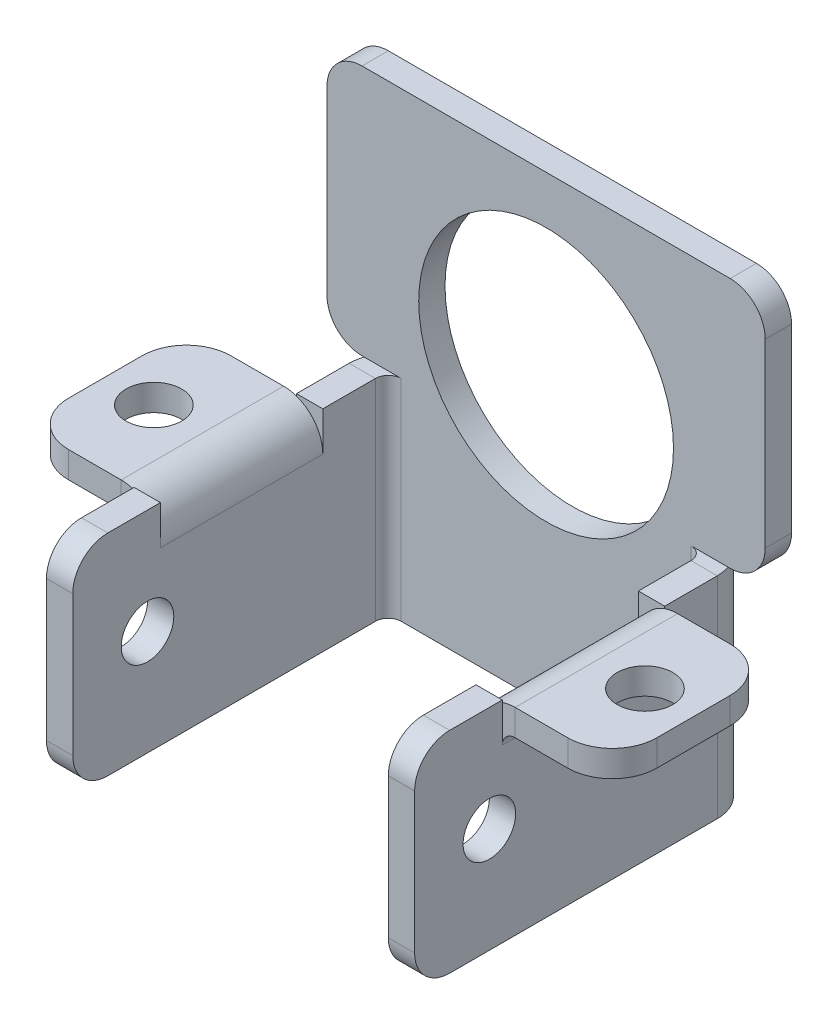
SolidWorks part; units mm, degrees
note: The reader was unsure of these and kept them because the rebuilt part matched: flange length of "Edge-Flange1", "Edge-Flange3".
material "Wrought Stainless Steel"
ref_plane "Front Plane" through (0, 0, 0) normal (0, 0, 1) x (1, 0, 0)
ref_plane "Top Plane" through (0, 0, 0) normal (0, 1, 0) x (1, 0, 0)
ref_plane "Right Plane" through (0, 0, 0) normal (1, 0, 0) x (0, 0, -1)
sketch "Sketch1" plane through (0, 0, 0) normal (0, 0, 1) x (1, 0, 0)
  line L8 (-9, -16.3187) -> (9, -16.3187) construction
  line L9 (-9, -16.3187) -> (9, -16.3187)
  line L10 (-12.5, -4.3187) -> (-9, -4.3187)
  line L11 (12.5, -4.3187) -> (9, -4.3187)
  line L14 (-8.7313, -10.3187) -> (8.7312, -10.3187) construction
  line L16 (-9, -12) -> (-9, -15.3187)
  line L17 (-9, -15.3187) -> (9, -15.3187)
  line L18 (9, -15.3187) -> (9, -12)
  line L19 (11, -10) -> (12.5, -10)
  line L20 (12.5, -10) -> (12.5, 10)
  line L21 (12.5, 10) -> (-12.5, 10)
  line L22 (-12.5, 10) -> (-12.5, -10)
  line L23 (-12.5, -10) -> (-11, -10)
  line L24 (-9, -4.3187) -> (-9, -16.3187)
  line L26 (9, -16.3187) -> (9, -4.3187)
  line L28 (12.5, -4.3187) -> (12.5, 10)
  line L29 (12.5, 10) -> (-12.5, 10)
  line L30 (-12.5, 10) -> (-12.5, -4.3187)
  circle A4 centre (0, 0) radius 7.2667 construction
  circle A5 centre (0, 0) radius 7.2667
  arc A8 (11, -10) -> (9, -12) centre (11, -12) ccw
  arc A9 (-9, -12) -> (-11, -10) centre (-11, -12) ccw
  dimension "D1" = 1
  dimension "D2" = 6
sheet metal parameters "Sheet-Metal1" thickness 1.5 parameters "D1"=0.7366
base flange "Base-Flange1" sketch "Sketch1" thickness 1.5 reverse thickness direction yes parameters "D1"=0.7366
edge flange "Edge-Flange1" sketch "Sketch7" flange profiles "Sketch7", "Sketch8" flange angle 90 flange length 18 bend radius 0.7366 thickness 1.5 parameters "D6"=10, "D8"=0.254
sketch "Sketch7" plane through (-9, 0, 1.5) normal (-1, 0, 0) x (0, -1, 0)
  line L0 (4.3187, 0) -> (16.3187, 0) construction
  line L1 (4.3187, 0) -> (16.3187, 0)
  line L2 (4.3187, 0) -> (4.3187, 18)
  line L3 (4.3187, 18) -> (16.3187, 18)
  line L4 (16.3187, 18) -> (16.3187, 0)
sketch "Sketch8" plane through (9, 0, 1.5) normal (1, 0, 0) x (0, 1, 0)
  line L0 (-16.3187, 0) -> (-4.3187, 0) construction
  line L1 (-16.3187, 0) -> (-4.3187, 0)
  line L2 (-16.3187, 0) -> (-16.3187, 18)
  line L3 (-16.3187, 18) -> (-4.3187, 18)
  line L4 (-4.3187, 18) -> (-4.3187, 0)
bend "EdgeBend1" bend radius 0.7366 bend angle 90 parameters "D5"=1
bend "EdgeBend2" bend radius 0.7366 bend angle 90 parameters "D5"=2
sketch "Sketch9" plane through (10.5, 0, 0) normal (1, 0, 0) x (0, 0, -1)
  line L0 (-2.2366, -4.3187) -> (-2.2366, -16.3187) construction
  line L1 (-19.5, -16.3187) -> (-2.2366, -16.3187) construction
  circle A0 centre (-15.2366, -10.3187) radius 1.5
  dimension "D1" = 13
  dimension "D2" = 6
  dimension "D3" = 3
extrude "Cut-Extrude1" cut sketch "Sketch9" against normal through all
fillet "Fillet1" radius 2 8 edges at (-12.5, -4.3187, 0.75) (-12.5, 10, 0.75) (-9.75, -16.3187, 19.5) (-9.75, -4.3187, 19.5) (9.75, -16.3187, 19.5) (9.75, -4.3187, 19.5) (12.5, 10, 0.75) (12.5, -4.3187, 0.75)
edge flange "Edge-Flange3" sketch "Sketch19" flange angle 90 flange length 6.2766 flange position material inside bend radius 0.7366 thickness 1.5 parameters "D6"=10
sketch "Sketch19" plane through (10.5, -4.3187, 0) normal (0, 1, 0) x (0, 0, 1)
  line L0 (2.2366, 0) -> (17.5, 0) construction
  line L1 (5.2366, 0) -> (14.5, 0)
  line L2 (5.2366, 0) -> (5.2366, 6.2766)
  line L3 (5.2366, 6.2766) -> (14.5, 6.2766)
  line L4 (14.5, 6.2766) -> (14.5, 0)
  dimension "D1" = 3
  dimension "D2" = 3
bend "EdgeBend5" bend radius 0.7366 bend angle 90 parameters "D5"=3
fillet "Fillet2" radius 2.54 2 edges at (16.7766, -5.0687, 5.2366) (16.7766, -5.0687, 14.5)
mirror "Mirror1" about plane through (0, 0, 0) normal (1, 0, 0) of "Fillet2", "Edge-Flange3"
bend "MirrorBend1" bend radius 0.7366 bend angle 90 parameters "D5"=4
sketch "Sketch20" plane through (0, -4.3188, 0) normal (0, 1, 0) x (1, 0, 0)
  line L0 (-11.2366, -9.8683) -> (-16.7766, -9.8683) construction
  line L1 (-11.2366, -5.2366) -> (-11.2366, -14.5) construction
  line L2 (-16.7766, -11.96) -> (-16.7766, -7.7766) construction
  line L3 (11.2366, -9.8683) -> (16.7766, -9.8683) construction
  line L4 (11.2366, -14.5) -> (11.2366, -5.2366) construction
  line L5 (16.7766, -11.96) -> (16.7766, -7.7766) construction
  circle A0 centre (14.0066, -9.8683) radius 1.5875
  circle A1 centre (-14.0066, -9.8683) radius 1.5875
  dimension "D1" = 3.175
extrude "Cut-Extrude3" cut sketch "Sketch20" against normal blind 2.54
ref_plane "Center Plane" through (0, -10.3187, 0) normal (0, 1, 0) x (-1, 0, 0)
flat pattern "Flat-Pattern1" [suppressed]
sketch "Bend-Lines1" plane through (0, 0, 1.5) normal (0, 0, 1) x (1, 0, 0)
  line L0 (-13.5985, -5.3878) -> (-22.8619, -5.3878) construction
  line L1 (13.5985, -5.3878) -> (22.8619, -5.3878) construction
  line L2 (9.431, -4.3187) -> (9.431, -16.3187) construction
  line L3 (-9.431, -16.3187) -> (-9.431, -4.3187) construction
  line L4 (-13.5985, -5.3878) -> (-22.8619, -5.3878) construction
  line L5 (13.5985, -5.3878) -> (22.8619, -5.3878) construction
  line L6 (9.431, -4.3187) -> (9.431, -16.3187) construction
  line L7 (-9.431, -16.3187) -> (-9.431, -4.3187) construction
bend of the flat pattern "Flatten-<EdgeBend1>1"
bend of the flat pattern "Flatten-<EdgeBend2>1"
bend of the flat pattern "Flatten-<EdgeBend5>1"
bend of the flat pattern "Flatten-<MirrorBend1>1"
